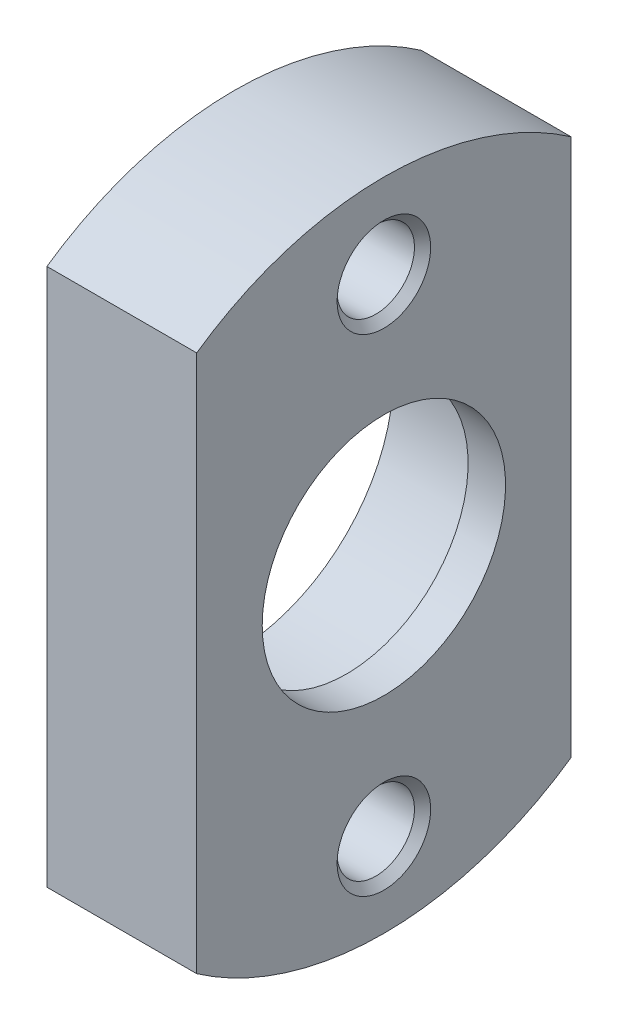
SolidWorks part; units mm, degrees
material "Q235A"
ref_plane "前视基准面" through (0, 0, 0) normal (0, 0, 1) x (1, 0, 0)
ref_plane "上视基准面" through (0, 0, 0) normal (0, 1, 0) x (1, 0, 0)
ref_plane "右视基准面" through (0, 0, 0) normal (1, 0, 0) x (0, 0, -1)
sketch "草图1" plane through (0, 0, 0) normal (0, 0, 1) x (1, 0, 0)
  line L0 (-4, 17.5) -> (-4, 8.5)
  line L1 (-4, 8.5) -> (2, 8.5)
  line L2 (2, 8.5) -> (2, 6.5)
  line L3 (2, 6.5) -> (4, 6.5)
  line L4 (4, 6.5) -> (4, 17.5)
  line L5 (4, 17.5) -> (-4, 17.5)
  line L6 (4, 0) -> (-4, 0) construction
revolve "旋转1" add sketch "草图1" angle 360 about L6 reverse direction yes
ref_plane "基准面1" through (0, 0, 0) normal (0, 0, 1) x (1, 0, 0)
sketch "草图2" plane through (0, 0, 0) normal (1, 0, 0) x (0, 0, -1)
  line L0 (-10, -17.5) -> (10, -17.5)
  line L1 (10, -17.5) -> (10, 17.5)
  line L2 (10, 17.5) -> (-10, 17.5)
  line L3 (-10, 17.5) -> (-10, -17.5)
  circle A0 centre (0, 0) radius 100
extrude "切除-拉伸1" cut sketch "草图2" along normal blind 8 and the other way blind 8
ref_plane "基准面2" through (0, 0, 0) normal (0, 0, 1) x (1, 0, 0)
sketch "草图3" plane through (0, 0, 0) normal (0, 0, 1) x (1, 0, 0)
  line L0 (-4, -13) -> (-4, -10.5)
  line L1 (-4, -10.5) -> (-3.567, -10.933)
  line L2 (-3.567, -10.933) -> (3.567, -10.933)
  line L3 (3.567, -10.933) -> (4, -10.5)
  line L4 (4, -10.5) -> (4, -13)
  line L5 (4, -13) -> (-4, -13)
  line L6 (4, -13) -> (-4, -13) construction
revolve "切除-旋转1" cut sketch "草图3" angle 360 about L6 reverse direction yes
cosmetic thread "装饰螺纹线1" parameters "D1"=8, "D2"=5
sketch "草图4" plane through (0, 0, 0) normal (0, 0, 1) x (1, 0, 0)
  line L0 (-4, 13) -> (-4, 15.5)
  line L1 (-4, 15.5) -> (-3.567, 15.067)
  line L2 (-3.567, 15.067) -> (3.567, 15.067)
  line L3 (3.567, 15.067) -> (4, 15.5)
  line L4 (4, 15.5) -> (4, 13)
  line L5 (4, 13) -> (-4, 13)
  line L6 (4, 13) -> (-4, 13) construction
revolve "切除-旋转2" cut sketch "草图4" angle 360 about L6 reverse direction yes
cosmetic thread "装饰螺纹线2" parameters "D1"=8, "D2"=5
ref_plane "基准面3" through (0, 0, 0) normal (0, 0, 1) x (1, 0, 0)
ref_plane "基准面4" through (0, 0, 0) normal (0, 0, 1) x (1, 0, 0)
ref_plane "基准面5" through (-4, 0, 0) normal (1, 0, 0) x (0, 0, -1)
ref_plane "基准面6" through (4, 0, 0) normal (1, 0, 0) x (0, 0, -1)
ref_plane "to_bearings XY" through (-4, 0, 0) normal (1, 0, 0) x (0, 0, -1)
ref_plane "to_bearings XZ" through (0, 0, 0) normal (0, -1, 0) x (-1, 0, 0)
ref_plane "to_bearings YZ" through (0, 0, 0) normal (0, 0, -1) x (-1, 0, 0)
ref_axis "to_bearings X" through (-4, 0, 80.9) along (0, 0, -1)
ref_axis "to_bearings Y" through (-4, -50, 0) along (0, 1, 0)
ref_axis "to_bearings Z" through (80.9, 0, 0) along (-1, 0, 0)
sketch3d "to_bearings"
  point P0 (-4, 0, 0)
ref_plane "bgcab_to_rring XY" through (4, 0, 0) normal (1, 0, 0) x (0, 0, -1)
ref_plane "bgcab_to_rring XZ" through (0, 0, 0) normal (0, -1, 0) x (-1, 0, 0)
ref_plane "bgcab_to_rring YZ" through (0, 0, 0) normal (0, 0, -1) x (-1, 0, 0)
ref_axis "bgcab_to_rring X" through (4, 0, 80.9) along (0, 0, -1)
ref_axis "bgcab_to_rring Y" through (4, -50, 0) along (0, 1, 0)
ref_axis "bgcab_to_rring Z" through (80.9, 0, 0) along (-1, 0, 0)
sketch3d "bgcab_to_rring"
  point P0 (4, 0, 0)
ref_plane "housing_to_dummy XY" through (0, 0, 0) normal (0, 0, 1) x (1, 0, 0)
ref_plane "housing_to_dummy XZ" through (0, 0, 0) normal (0, -1, 0) x (-1, 0, 0)
ref_plane "housing_to_dummy YZ" through (0, 0, 0) normal (1, 0, 0) x (0, 0, -1)
ref_axis "housing_to_dummy X" through (-80.9, 0, 0) along (1, 0, 0)
ref_axis "housing_to_dummy Y" through (0, -50, 0) along (0, 1, 0)
ref_axis "housing_to_dummy Z" through (0, 0, 80.9) along (0, 0, -1)
sketch3d "housing_to_dummy"
  point P0 (0, 0, 0)
